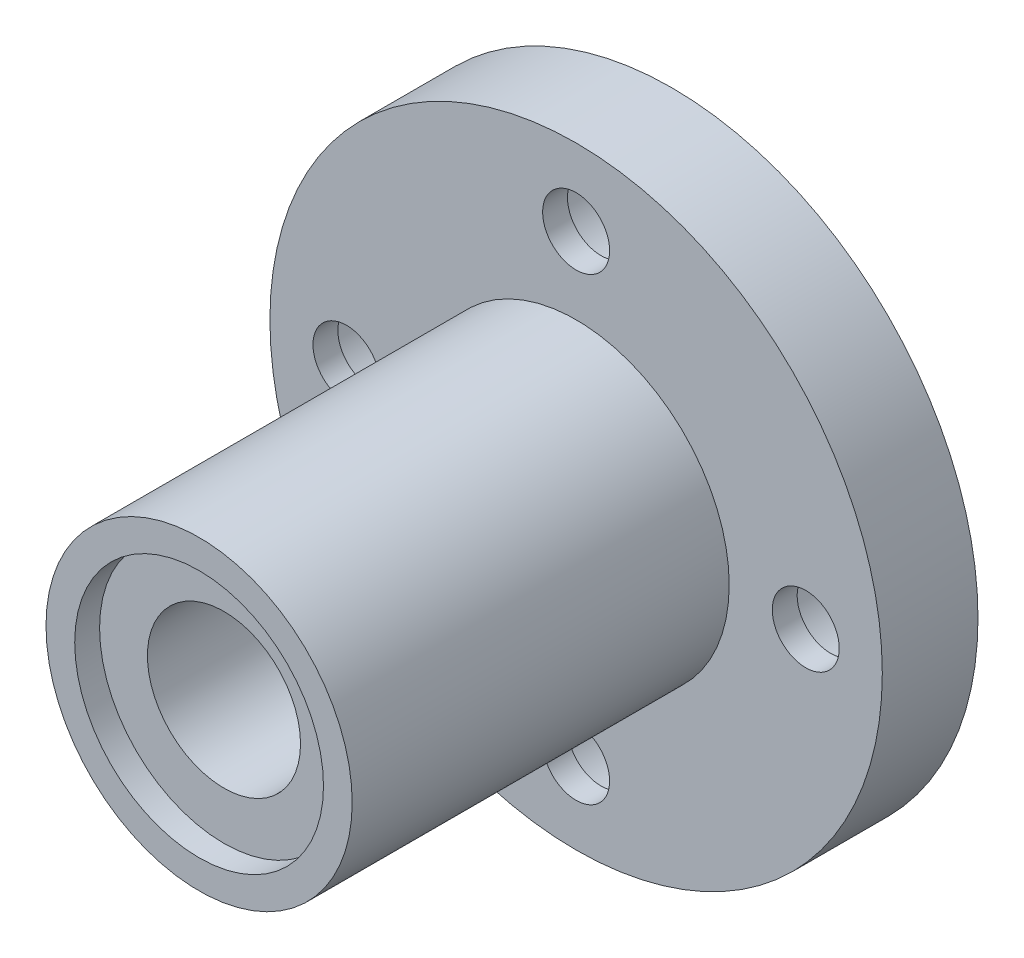
SolidWorks part; units mm, degrees
ref_plane "Ön Düzlem" through (0, 0, 0) normal (0, 0, 1) x (1, 0, 0)
ref_plane "Üst Düzlem" through (0, 0, 0) normal (0, 1, 0) x (1, 0, 0)
ref_plane "Sağ Düzlem" through (0, 0, 0) normal (1, 0, 0) x (0, 0, -1)
sketch "Çizim1" plane through (0, 0, 0) normal (0, 0, 1) x (1, 0, 0)
  circle A0 centre (0, 0) radius 16
  dimension "D1" = 32
extrude "Yükseklik-Ekstrüzyon1" add sketch "Çizim1" along normal blind 5
sketch "Çizim2" plane through (0, 0, 5) normal (0, 0, 1) x (1, 0, 0)
  circle A0 centre (0, 0) radius 8
  dimension "D1" = 16
extrude "Yükseklik-Ekstrüzyon2" add sketch "Çizim2" along normal blind 19.7
sketch "Çizim3" plane through (0, 0, 24.7) normal (0, 0, 1) x (1, 0, 0)
  circle A0 centre (0, 0) radius 4
  dimension "D1" = 8
extrude "Kes-Ekstrüzyon1" cut sketch "Çizim3" against normal up to next
sketch "Çizim4" plane through (0, 0, 0) normal (0, 0, -1) x (-1, 0, 0)
  circle A0 centre (0, 0) radius 12 construction
  circle A1 centre (-12, 0) radius 1.75
  circle A2 centre (0, 12) radius 1.75
  circle A3 centre (12, 0) radius 1.75
  circle A4 centre (0, -12) radius 1.75
  circle A5 centre (0, 12) radius 3.25
  circle A6 centre (12, 0) radius 3.25
  circle A7 centre (0, -12) radius 3.25
  circle A8 centre (-12, 0) radius 3.25
  dimension "D1" = 24
  dimension "D2" = 3.5
  dimension "D3" = 6.5
extrude "Kes-Ekstrüzyon2" cut sketch "Çizim4" against normal up to next contours A2 | A3 | A4 | A1 region at (12, 0, 0) region at (0, 12, 0) region at (-12, 0, 0) region at (0, -12, 0)
extrude "Kes-Ekstrüzyon3" cut sketch "Çizim4<3>" against normal blind 3.7
sketch "Çizim4<3>" plane through (0, 0, 0) normal (0, 0, -1) x (-1, 0, 0) same geometry as "Çizim4"
sketch "Çizim5" plane through (0, 0, 24.7) normal (0, 0, 1) x (1, 0, 0)
  circle A0 centre (0, 0) radius 6.5
  dimension "D1" = 13
extrude "Kes-Ekstrüzyon4" cut sketch "Çizim5" against normal blind 1.3
extrude "Kes-Ekstrüzyon5" cut sketch "Çizim5<2>" along normal blind 1.3 from surface starting at face at (-3.25, 12, 0)
sketch "Çizim5<2>" plane through (0, 0, 24.7) normal (0, 0, 1) x (1, 0, 0) same geometry as "Çizim5"
